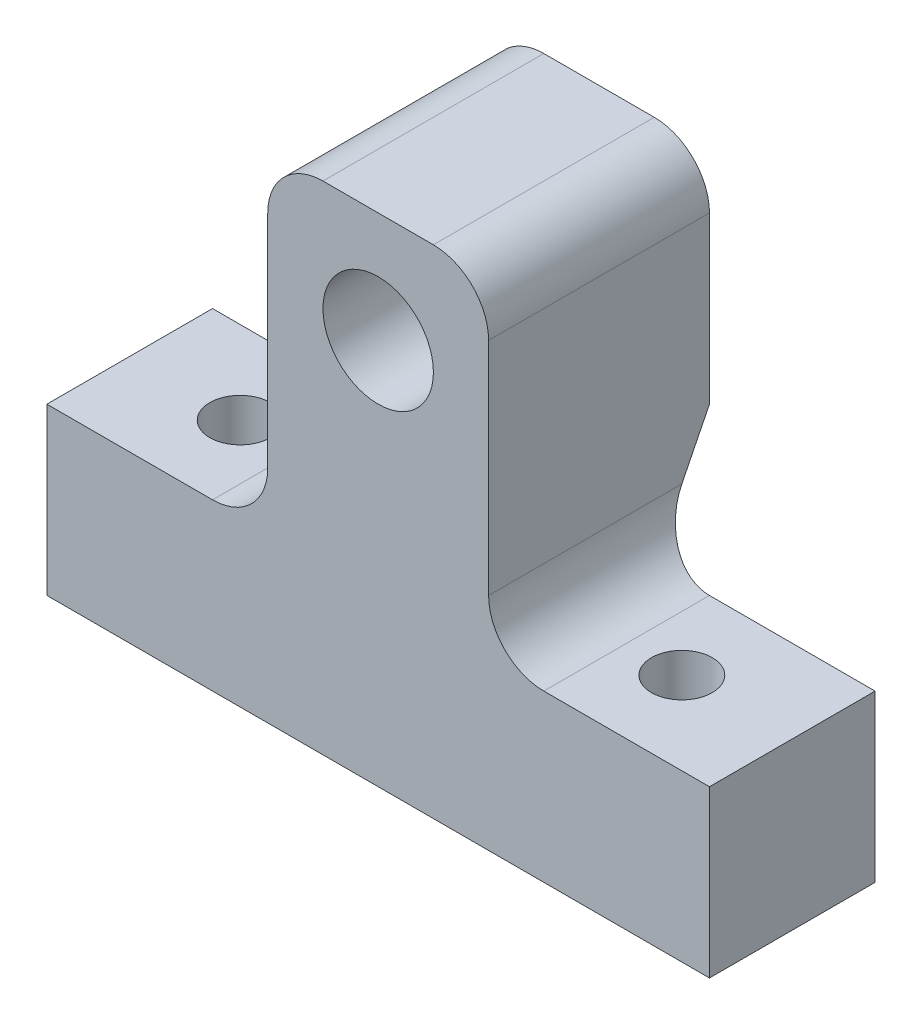
SolidWorks part; units mm, degrees
ref_plane "Front Plane" through (0, 0, 0) normal (0, 0, 1) x (1, 0, 0)
ref_plane "Top Plane" through (0, 0, 0) normal (0, 1, 0) x (1, 0, 0)
ref_plane "Right Plane" through (0, 0, 0) normal (1, 0, 0) x (0, 0, -1)
sketch "Sketch1" plane through (0, 0, 0) normal (0, 0, 1) x (1, 0, 0)
  line L0 (10, 7.5) -> (30, 7.5)
  line L1 (-30, -7.5) -> (30, -7.5)
  line L2 (-30, -7.5) -> (-30, 7.5)
  line L3 (-30, 7.5) -> (-10, 7.5)
  line L4 (30, -7.5) -> (30, 7.5)
  line L5 (-30, -7.5) -> (30, 7.5) construction
  line L6 (-30, 7.5) -> (30, -7.5) construction
  line L7 (-10, 37.5) -> (10, 37.5)
  line L8 (-10, 37.5) -> (-10, 7.5)
  line L10 (10, 37.5) -> (10, 7.5)
  line L11 (-10, 37.5) -> (10, 7.5) construction
  line L12 (-10, 7.5) -> (10, 37.5) construction
  circle A0 centre (0, 27.5) radius 5
  point P0 (0, 0)
  point P6 (0, 22.5)
  point P11 (0, 0)
  point P12 (0, 25)
  dimension "D5" = 10
  dimension "D1" = 15
  dimension "D2" = 60
  dimension "D3" = 20
  dimension "D4" = 30
  dimension "D6" = 20
extrude "Boss-Extrude1" add sketch "Sketch1" along normal mid plane 15
sketch "Sketch2" plane through (0, 7.5, 0) normal (0, 1, 0) x (1, 0, 0)
  line L0 (-20, 0) -> (20, 0) construction
  circle A0 centre (-20, 0) radius 2.75
  circle A1 centre (20, 0) radius 2.75
  point P3 (0, 0)
  dimension "D2" = 5.5
  dimension "D1" = 40
extrude "Cut-Extrude1" cut sketch "Sketch2" against normal through all
sketch "Sketch3" plane through (0, 0, -7.5) normal (0, 0, -1) x (-1, 0, 0)
  line L0 (-10, 37.5) -> (10, 37.5) construction
  line L1 (-10, 37.5) -> (10, 37.5)
  line L2 (-10, 37.5) -> (-10, 17.5)
  line L3 (-10, 7.5) -> (-10, 37.5) construction
  line L4 (-10, 17.5) -> (10, 17.5)
  line L5 (10, 37.5) -> (10, 7.5) construction
  line L6 (10, 17.5) -> (10, 37.5)
  circle A0 centre (0, 27.5) radius 5 construction
  circle A1 centre (0, 27.5) radius 5
  point P5 (-10, 27.5)
  point P12 (0, 0)
extrude "Boss-Extrude2" add sketch "Sketch3" along normal blind 5
sketch "Sketch4" plane through (0, 0, -12.5) normal (0, 0, -1) x (-1, 0, 0)
  circle A0 centre (0, 27.5) radius 5 construction
  circle A1 centre (0, 27.5) radius 5
  circle A2 centre (0, 27.5) radius 2.75
  dimension "D1" = 5.5
extrude "Boss-Extrude3" add sketch "Sketch4" against normal blind 1
chamfer "Chamfer1" distance 10 distance2 5 1 edges at (0, 17.5, -7.5) first distance on face at (0, 6.25, -7.5)
fillet "Fillet2" radius 5 4 edges at (-10, 7.5, 0) (10, 7.5, 0) (10, 37.5, -2.5) (-10, 37.5, -2.5)
